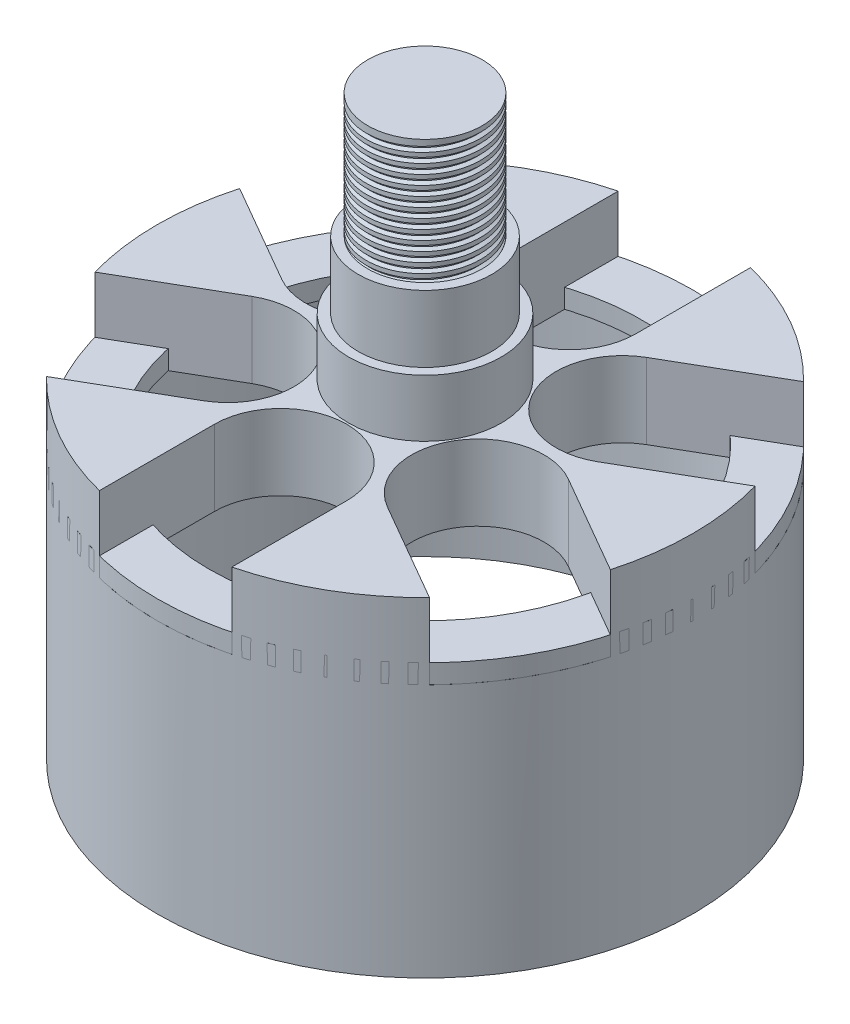
SolidWorks part; units mm, degrees
ref_plane "Front Plane" through (0, 0, 0) normal (0, 0, 1) x (1, 0, 0)
ref_plane "Top Plane" through (0, 0, 0) normal (0, 1, 0) x (1, 0, 0)
ref_plane "Right Plane" through (0, 0, 0) normal (1, 0, 0) x (0, 0, -1)
sketch "Sketch1" plane through (0, 0, 0) normal (0, 1, 0) x (1, 0, 0)
  circle A0 centre (0, 0) radius 14.03
  circle A1 centre (0, 0) radius 13.03
  dimension "D1" = 28.06
  dimension "D2" = 1
extrude "Boss-Extrude1" add sketch "Sketch1" along normal blind 17.27 contours A0
extrude "Cut-Extrude1" cut sketch "Sketch1<3>" along normal blind 13.31 contours A1
sketch "Sketch1<3>" plane through (0, 0, 0) normal (0, 1, 0) x (1, 0, 0) same geometry as "Sketch1"
sketch "Sketch2" plane through (0, 17.27, 0) normal (0, 1, 0) x (1, 0, 0)
  line L0 (0, -7.57) -> (0, -14.03) construction
  line L1 (3.47, -7.57) -> (3.47, -13.5941)
  line L2 (-3.47, -7.57) -> (-3.47, -13.5941)
  line L3 (0, 14.03) -> (0, 0) construction
  line L4 (-8.2908, -0.7799) -> (-13.5079, -3.792)
  line L5 (-4.8208, -6.7901) -> (-10.0379, -9.8022)
  line L6 (-4.8208, 6.7901) -> (-10.0379, 9.8022)
  line L7 (-8.2908, 0.7799) -> (-13.5079, 3.792)
  line L8 (3.47, 7.57) -> (3.47, 13.5941)
  line L9 (-3.47, 7.57) -> (-3.47, 13.5941)
  line L10 (8.2908, 0.7799) -> (13.5079, 3.792)
  line L11 (4.8208, 6.7901) -> (10.0379, 9.8022)
  line L12 (4.8208, -6.7901) -> (10.0379, -9.8022)
  line L13 (8.2908, -0.7799) -> (13.5079, -3.792)
  circle A0 centre (0, 0) radius 4
  arc A1 (3.47, -7.57) -> (-3.47, -7.57) centre (0, -7.57) ccw
  circle A3 centre (0, 0) radius 14.03
  circle A4 centre (0, 0) radius 14.03 construction
  arc A5 (3.47, -13.5941) -> (-3.47, -13.5941) centre (0, 0) cw
  arc A6 (-10.0379, -9.8022) -> (-13.5079, -3.792) centre (0, 0) cw
  arc A7 (-4.8208, -6.7901) -> (-8.2908, -0.7799) centre (-6.5558, -3.785) ccw
  arc A8 (-13.5079, 3.792) -> (-10.0379, 9.8022) centre (0, 0) cw
  arc A9 (-8.2908, 0.7799) -> (-4.8208, 6.7901) centre (-6.5558, 3.785) ccw
  arc A10 (-3.47, 13.5941) -> (3.47, 13.5941) centre (0, 0) cw
  arc A11 (-3.47, 7.57) -> (3.47, 7.57) centre (0, 7.57) ccw
  arc A12 (10.0379, 9.8022) -> (13.5079, 3.792) centre (0, 0) cw
  arc A13 (4.8208, 6.7901) -> (8.2908, 0.7799) centre (6.5558, 3.785) ccw
  arc A14 (13.5079, -3.792) -> (10.0379, -9.8022) centre (0, 0) cw
  arc A15 (8.2908, -0.7799) -> (4.8208, -6.7901) centre (6.5558, -3.785) ccw
  point P11 (0, -4.1)
  point P15 (0, -4)
  point P43 (0, 0)
  dimension "D1" = 8
  dimension "D3" = 28.06
  dimension "D5" = 3.47
  dimension "D2" = 6.94
  dimension "D4" = 0.1
  dimension "D6" = 6
extrude "Cut-Extrude2" cut sketch "Sketch2" against normal up to surface (3.96 mm away) contours A9 L6 A8 L7 | A11 L8 A10 L9 | A13 L10 A12 L11 | L13 A14 L12 A15 | L1 A5 L2 A1 | L5 A6 L4 A7 up to face at (0, 13.31, 13.03)
extrude "Boss-Extrude2" add sketch "Sketch2<3>" along normal blind 3 contours A0
sketch "Sketch2<3>" plane through (0, 17.27, 0) normal (0, 1, 0) x (1, 0, 0) same geometry as "Sketch2"
sketch "Sketch3" plane through (0, 20.27, 0) normal (0, 1, 0) x (1, 0, 0)
  circle A0 centre (0, 0) radius 3.5
  dimension "D1" = 7
extrude "Boss-Extrude3" add sketch "Sketch3" along normal blind 3.5
sketch "Sketch4" plane through (0, 23.77, 0) normal (0, 1, 0) x (1, 0, 0)
  circle A0 centre (0, 0) radius 3
  dimension "D1" = 6
extrude "Boss-Extrude4" add sketch "Sketch4" along normal blind 6.5
sketch "Sketch5" plane through (0, 13.31, 0) normal (0, 1, 0) x (1, 0, 0)
  circle A0 centre (0, 0) radius 11.33
  circle A1 centre (0, 0) radius 14.03 construction
  circle A3 centre (0, 0) radius 14.03
  dimension "D1" = 2.7
  dimension "D2" = 28.06
extrude "Boss-Extrude5" add sketch "Sketch5" along normal blind 1 separate body contours A0 | A3
thread "Thread1" pitch 0.3175 method cut profile "Thread Profile1" start angle 0, offset 0, length 0, pitch 0.5, diameter 6
ref_plane "Plane1" through (-3, 30.27, 0) normal (0, 0, 1) x (-1, 0, 0)
sketch "Thread Profile1" plane through (-3, 30.27, 0) normal (0, 0, 1) x (-1, 0, 0)
  line L0 (0, 0) -> (0, 0.3175) construction
  line L11 (0, 0) -> (0, 0.2778)
  line L12 (0, 0.2778) -> (-0.1719, 0.1786)
  line L13 (-0.1719, 0.1786) -> (-0.1719, 0.0992)
  line L15 (-0.1719, 0.0992) -> (0, 0)
  line L17 (-0.1719, 0.1389) -> (0, 0.1389) construction
  point P2 (0, 0)
  dimension "Pitch" = 0.3175
  dimension "Profile_Angle" = 60
  dimension "Profile_Land" = 0.0794
  dimension "Profile_Height" = 0.1719
